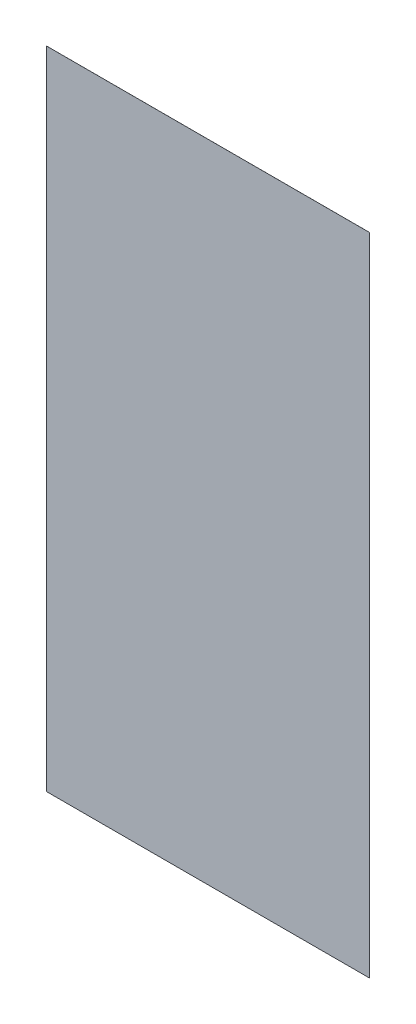
SolidWorks part; units mm, degrees
ref_plane "前视基准面" through (0, 0, 0) normal (0, 0, 1) x (1, 0, 0)
ref_plane "上视基准面" through (0, 0, 0) normal (0, 1, 0) x (1, 0, 0)
ref_plane "右视基准面" through (0, 0, 0) normal (1, 0, 0) x (0, 0, -1)
sketch "草图1" plane through (0, 0, 0) normal (0, 0, 1) x (1, 0, 0)
  line L1 (-50, 100) -> (50, 100)
  line L2 (-50, 100) -> (-50, -100)
  line L3 (-50, -100) -> (50, -100)
  line L4 (50, 100) -> (50, -100)
  line L5 (-50, 100) -> (50, -100) construction
  line L6 (-50, -100) -> (50, 100) construction
  point P0 (0, 0)
  point P6 (25, 50)
  dimension "D1" = 100
  dimension "D2" = 200
extrude "凸台-拉伸1" add sketch "草图1" along normal blind 0.01
